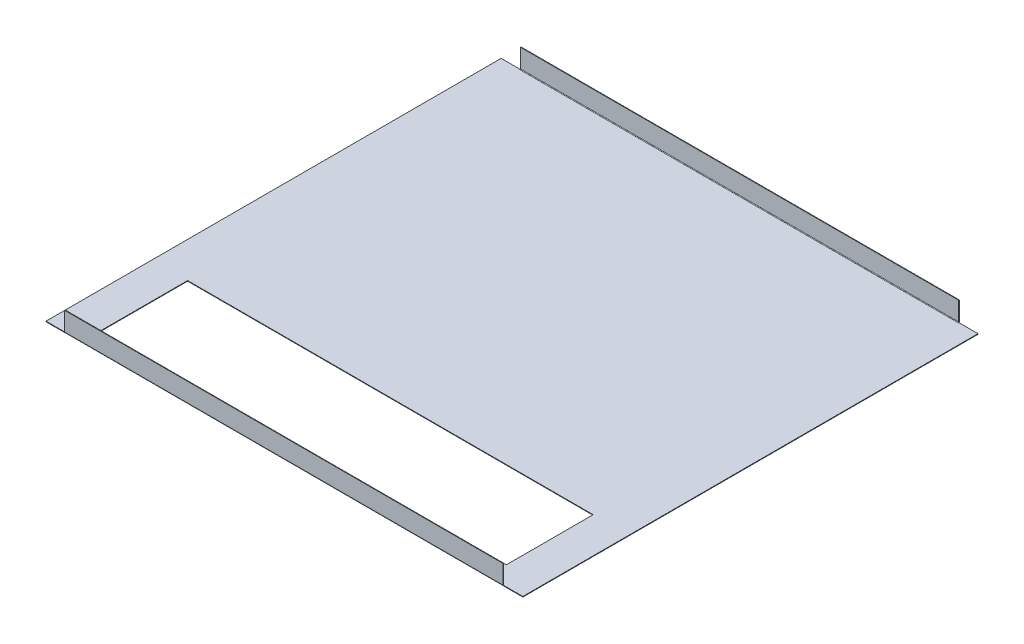
SolidWorks part; units mm, degrees
note: The reader was unsure of these and kept them because the rebuilt part matched: flange length of "Edge-Flange1", "Edge-Flange2".
material "AISI 1020 Steel, Cold Rolled"
ref_plane "Front Plane" through (0, 0, 0) normal (0, 0, 1) x (1, 0, 0)
ref_plane "Top Plane" through (0, 0, 0) normal (0, 1, 0) x (1, 0, 0)
ref_plane "Right Plane" through (0, 0, 0) normal (1, 0, 0) x (0, 0, -1)
sketch "Sketch1" plane through (0, 0, 0) normal (0, 1, 0) x (1, 0, 0)
  line L0 (0, 472.5) -> (0, -472.5) construction
  line L1 (-495, -472.5) -> (495, -472.5)
  line L2 (-495, -472.5) -> (-495, 472.5)
  line L3 (-495, 472.5) -> (495, 472.5)
  line L4 (495, -472.5) -> (495, 472.5)
  line L5 (-495, -472.5) -> (495, 472.5) construction
  line L6 (-495, 472.5) -> (495, -472.5) construction
  line L8 (-421, -252.5) -> (421, -252.5)
  line L9 (-421, -252.5) -> (-421, -432.5)
  line L10 (-421, -432.5) -> (421, -432.5)
  line L11 (421, -252.5) -> (421, -432.5)
  line L12 (-421, -252.5) -> (421, -432.5) construction
  line L13 (-421, -432.5) -> (421, -252.5) construction
  point P0 (0, 0)
  point P8 (0, -342.5)
  dimension "D1" = 990
  dimension "D2" = 945
  dimension "D3" = 842
  dimension "D4" = 180
  dimension "D5" = 40
sheet metal parameters "Sheet-Metal1" thickness 1.2 parameters "D1"=1.2
base flange "Base-Flange1" sketch "Sketch1" thickness 1.2 reverse thickness direction no parameters "D1"=1.2
edge flange "Edge-Flange1" sketch "Sketch9" flange angle 90 flange length 41.2 flange position material outside bend radius 1.2 thickness 1.2 relief none parameters "D6"=10, "D8"=0.1
sketch "Sketch9" plane through (0, 0, -472.5) normal (0, 0, -1) x (-1, 0, 0)
  line L0 (-495, 0) -> (495, 0) construction
  line L1 (-455, 0) -> (455, 0)
  line L2 (-455, 0) -> (-455, 40)
  line L3 (-455, 40) -> (455, 40)
  line L4 (455, 40) -> (455, 0)
  dimension "D1" = 40
  dimension "D2" = 40
bend "EdgeBend1" bend radius 1.2 bend angle 90 parameters "D5"=1
edge flange "Edge-Flange2" sketch "Sketch12" flange angle 90 flange length 41.2 flange position material outside bend radius 1.2 thickness 1.2 relief none parameters "D6"=10
sketch "Sketch12" plane through (0, 0, 472.5) normal (0, 0, 1) x (1, 0, 0)
  line L2 (-455, 0) -> (-455, 40)
  line L3 (-455, 40) -> (455, 40)
  line L4 (455, 40) -> (455, 0)
  line L5 (-495, 0) -> (495, 0) construction
  line L6 (-455, 0) -> (455, 0)
  dimension "D1" = 40
  dimension "D2" = 40
bend "EdgeBend2" bend radius 1.2 bend angle 90 parameters "D5"=2
flat pattern "Flat-Pattern1" [suppressed]
sketch "Bend-Lines1" plane through (0, 0, 0) normal (0, 1, 0) x (-1, 0, 0)
  line L0 (-455, -471.4666) -> (455, -471.4666) construction
  line L1 (-455, -471.4666) -> (455, -471.4666) construction
  line L2 (455, 471.4666) -> (-455, 471.4666) construction
  line L3 (455, 471.4666) -> (-455, 471.4666) construction
bend of the flat pattern "Flatten-<EdgeBend1>1"
bend of the flat pattern "Flatten-<EdgeBend2>1"
